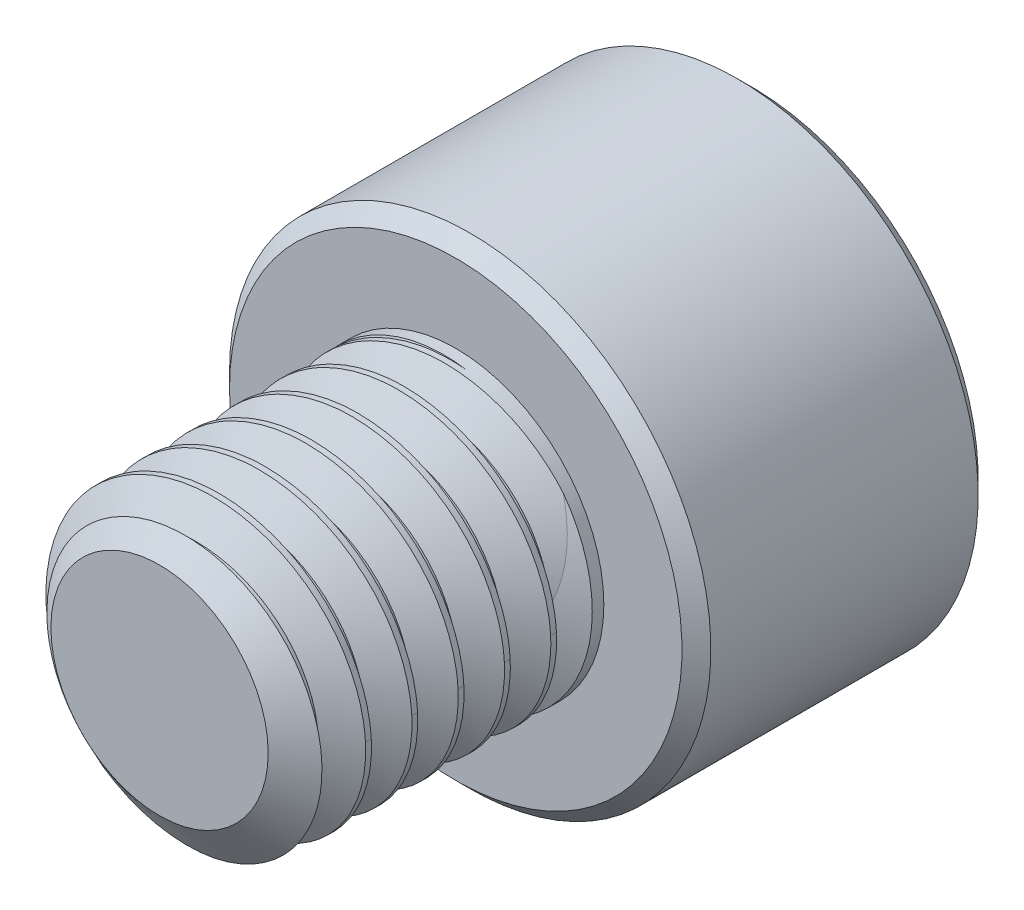
SolidWorks part; units mm, degrees
ref_plane "Front Plane" through (0, 0, 0) normal (0, 0, 1) x (1, 0, 0)
ref_plane "Top Plane" through (0, 0, 0) normal (0, 1, 0) x (1, 0, 0)
ref_plane "Right Plane" through (0, 0, 0) normal (1, 0, 0) x (0, 0, -1)
sketch "Sketch1" plane through (0, 0, 0) normal (0, 0, 1) x (1, 0, 0)
  circle A0 centre (0, 0) radius 4
  dimension "OD" = 8
extrude "Extrude1" add sketch "Sketch1" against normal blind 8
sketch "Sketch2" plane through (0, 0, 0) normal (0, 0, 1) x (1, 0, 0)
  circle A0 centre (0, 0) radius 4 construction
  circle A1 centre (0, 0) radius 4
curve "Helix/Spiral1" pitch 1.25 height 9.25 turns 7.4 parameters "pitch"=1.25
sketch "Sketch3" plane through (0, 0, 0) normal (1, 0, 0) x (0, 0, -1)
  line L0 (-1.0938, 4) -> (-0.625, 3.1881)
  line L1 (-0.625, 3.1881) -> (-0.4688, 3.1881)
  line L2 (-0.4688, 3.1881) -> (0, 4)
  line L3 (-1.0938, 4) -> (0, 4)
  line L4 (-0.5469, 4) -> (-0.5469, 3.1881) construction
  line L5 (-0.8594, 3.5941) -> (-0.2344, 3.5941) construction
  line L6 (0, 4) -> (0, -4) construction
  line L7 (0, -4) -> (8, -4) construction
  point P11 (5.625, -4)
  dimension "D1" = 0.1562
  dimension "D2" = 0.625
  dimension "D3" = 60
  dimension "D4" = 5.625
sweep "Cut-Sweep1" cut profiles "Sketch3" path "Helix/Spiral1" align with end faces yes
sketch "Sketch4" plane through (0, 0, 0) normal (1, 0, 0) x (0, 0, -1)
  line L0 (0.7464, 4) -> (0, 2.9341)
  line L1 (0, 2.9341) -> (0, 4)
  line L2 (0.7464, 4) -> (0, 4)
  line L3 (-1.0938, 4) -> (0, 4) construction
  line L4 (0, 0) -> (7.0209, 0) construction
  dimension "D1" = 55
  dimension "D2" = 0.254
revolve "Cut-Revolve1" cut sketch "Sketch4" angle 360 about L4
sketch "Sketch5" plane through (0, 0, 0) normal (1, 0, 0) x (0, 0, -1)
  line L0 (8, -0.6) -> (8, 3.4196) construction
  line L1 (8, 4) -> (84.1202, 4)
  line L2 (8, 4) -> (8, 0)
  line L3 (8, 0) -> (84, 0)
  line L4 (84, 3.6698) -> (84, 0)
  line L5 (84.1202, 4) -> (84, 3.6698)
  line L6 (0, 0) -> (9.9695, 0) construction
  point P3 (84, 4)
  point P10 (84, 4)
  dimension "D1" = 0.3302
  dimension "Thread min" = 84
  dimension "D3" = 20
revolve "partially thread" [suppressed] add sketch "Sketch5" angle 360 about L6
sketch "Sketch6" plane through (0, 0, -8) normal (0, 0, -1) x (-1, 0, 0)
  circle A0 centre (0, 0) radius 6.5
  dimension "head dia" = 13
extrude "Extrude2" add sketch "Sketch6" along normal blind 8
sketch "Sketch7" plane through (0, 0, -16) normal (0, 0, -1) x (-1, 0, 0)
  line L1 (0, 3.4641) -> (-3, 1.7321)
  line L2 (-3, 1.7321) -> (-3, -1.7321)
  line L3 (-3, -1.7321) -> (0, -3.4641)
  line L4 (0, -3.4641) -> (3, -1.7321)
  line L5 (3, -1.7321) -> (3, 1.7321)
  line L6 (3, 1.7321) -> (0, 3.4641)
  circle A0 centre (0, 0) radius 3 construction
  dimension "hex dia" = 6
extrude "Cut-Extrude1" cut sketch "Sketch7" against normal blind 4.5
sketch "Sketch8" plane through (0, 0, -16) normal (0, 0, -1) x (-1, 0, 0)
  circle A0 centre (0, 0) radius 3.4641
extrude "Cut-Extrude2" cut sketch "Sketch8" against normal through all draft 45
chamfer "Chamfer1" distance 0.39 angle 45 2 edges at (-6.5, 0, -16) (-6.5, 0, -8)
sketch "Sketch9" plane through (0, 0, 0) normal (1, 0, 0) x (0, 0, -1)
  line L0 (0, 4) -> (0, -4) construction
  line L1 (6.875, 4) -> (6.875, -4) construction
  dimension "D1" = 6.875
sketch "Sketch10" plane through (0, 0, 0) normal (1, 0, 0) x (0, 0, -1)
  line L0 (8, 4) -> (8, 0)
  line L1 (8, 4) -> (7.6875, 4)
  line L2 (7.6875, 4) -> (6.0306, 0)
  line L3 (8, 0) -> (6.0306, 0)
  line L4 (8, 6.11) -> (8, -6.11) construction
  dimension "D1" = 22.5
  dimension "D2" = 0.3125
revolve "Revolve1" add sketch "Sketch10" angle 360 about L3
equation "\"D3@Helix/Spiral1\" = \"screw length@Extrude1\"+\"pitch@Helix/Spiral1\""
equation "\"D1@Sketch3\" = \"pitch@Helix/Spiral1\"*.125"
equation "\"D2@Sketch3\" = \"pitch@Helix/Spiral1\"*.5"
equation "\"D1@Cut-Extrude1\" = \"hex dia@Sketch7\"*.75"
equation "\"D1@Chamfer1\" = \"head dia@Sketch6\"*.03"
equation "\"D1@Sketch9\" = \"pitch@Helix/Spiral1\"*5.5"
equation "\"D2@Sketch10\" = \"pitch@Helix/Spiral1\"*.25"
equation "\"D4@Sketch3\" = \"pitch@Helix/Spiral1\"*4.50"
